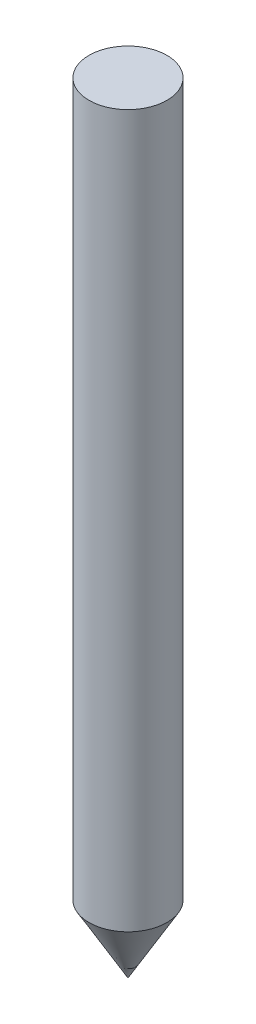
SolidWorks part; units mm, degrees
ref_plane "Front Plane" through (0, 0, 0) normal (0, 0, 1) x (1, 0, 0)
ref_plane "Top Plane" through (0, 0, 0) normal (0, 1, 0) x (1, 0, 0)
ref_plane "Right Plane" through (0, 0, 0) normal (1, 0, 0) x (0, 0, -1)
sketch "Sketch1" plane through (0, 0, 0) normal (0, 1, 0) x (1, 0, 0)
  circle A0 centre (0, 0) radius 6
  dimension "D1" = 12
extrude "Boss-Extrude1" add sketch "Sketch1" along normal blind 120
chamfer "Chamfer1" distance 6 angle 60 1 edges at (0, 0, 6) first distance on face at (0, 0, 6)
